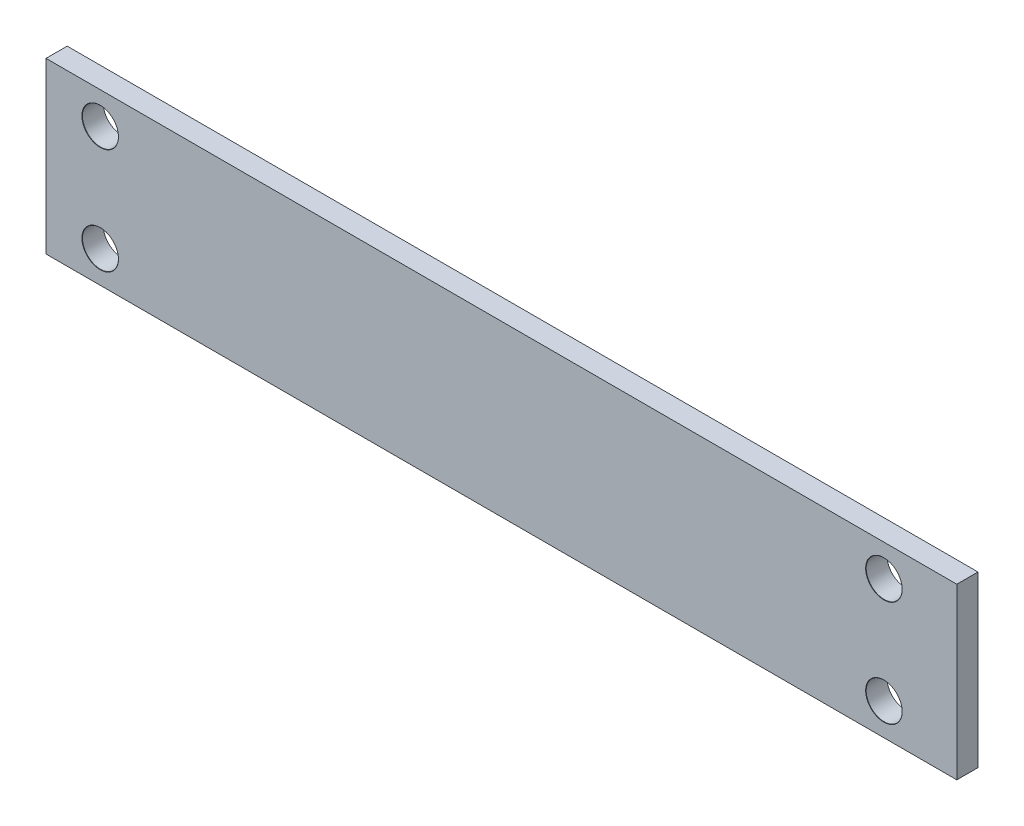
SolidWorks part; units mm, degrees
ref_plane "Front Plane" through (0, 0, 0) normal (0, 0, 1) x (1, 0, 0)
ref_plane "Top Plane" through (0, 0, 0) normal (0, 1, 0) x (1, 0, 0)
ref_plane "Right Plane" through (0, 0, 0) normal (1, 0, 0) x (0, 0, -1)
sketch "Sketch1" plane through (0, 0, 0) normal (0, 0, 1) x (1, 0, 0)
  line L1 (0, 0) -> (86, 0)
  line L2 (0, 0) -> (0, 16)
  line L3 (0, 16) -> (86, 16)
  line L4 (86, 0) -> (86, 16)
  dimension "D1" = 86
  dimension "D2" = 16
extrude "Boss-Extrude1" add sketch "Sketch1" along normal blind 2
sketch "Sketch4" plane through (0, 0, 2) normal (0, 0, 1) x (1, 0, 0)
  line L0 (5.1158, 3) -> (5.1158, 13)
  line L1 (5.1158, 13) -> (79.1158, 13)
  line L2 (79.1158, 3) -> (79.1158, 13)
  line L4 (5.1158, 8) -> (0, 8) construction
  line L5 (0, 16) -> (0, 0) construction
  point P0 (5.1158, 13)
  point P2 (5.1158, 3)
  point P4 (79.1158, 13)
  point P6 (79.1158, 3)
  dimension "D1" = 74
  dimension "D2" = 10
hole_wizard "M3 Clearance Hole1" positions "Sketch4" profile "Sketch3" hole size "M3" standard "DIN" end condition through all
sketch "Sketch3" plane through (5.1158, 13, 2) normal (1, 0, 0) x (0, -1, 0)
  line L0 (0, 0) -> (0, 2)
  line L1 (0, 2) -> (1.7, 2)
  line L2 (1.7, 2) -> (1.7, 0.025)
  line L3 (1.7, 0.025) -> (1.725, 0)
  line L5 (1.725, 0) -> (0, 0)
  line L6 (-1.7, 0.025) -> (-1.725, 0) construction
  line L11 (0, -6.35) -> (0, 107.95) construction
  dimension "Thru Hole Dia." = 3.4
  dimension "Thru Hole Depth" = 2
  dimension "Near C'Sink Dia." = 3.45
  dimension "Near C'Sink Angle" = 90
